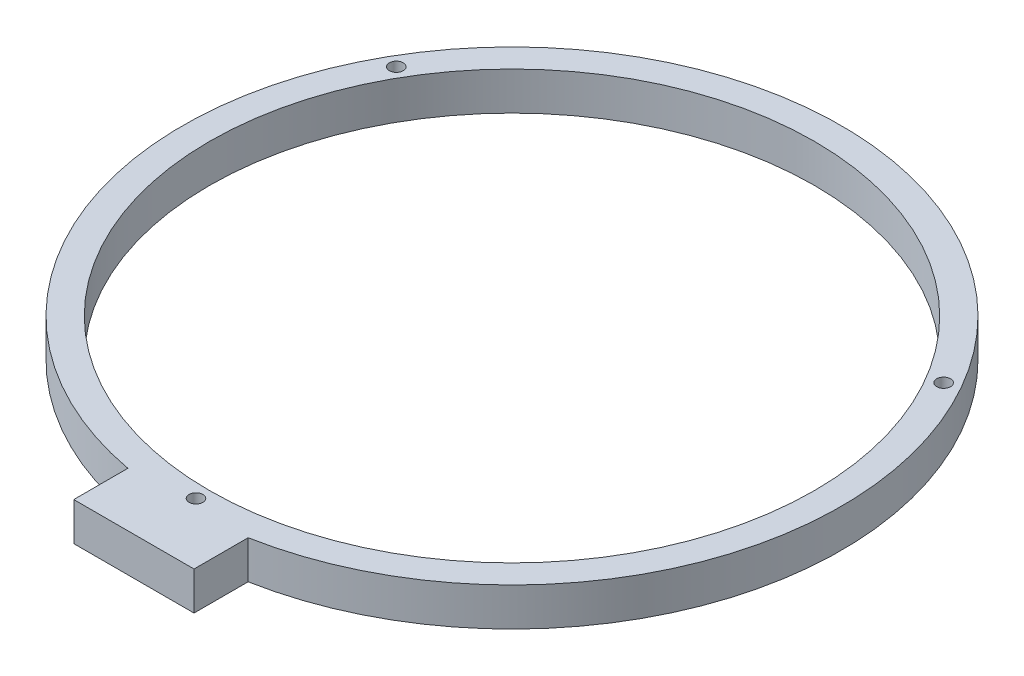
SolidWorks part; units mm, degrees
material "pla"
ref_plane "Front Plane" through (0, 0, 0) normal (0, 0, 1) x (1, 0, 0)
ref_plane "Top Plane" through (0, 0, 0) normal (0, 1, 0) x (1, 0, 0)
ref_plane "Right Plane" through (0, 0, 0) normal (1, 0, 0) x (0, 0, -1)
sketch "Sketch1" plane through (0, 0, 0) normal (0, 1, 0) x (1, 0, 0)
  line L0 (-10, -53.8799) -> (-10, -62.8799)
  line L1 (-10, -62.8799) -> (10, -62.8799)
  line L2 (10, -62.8799) -> (10, -53.8799)
  arc A0 (10, -53.8799) -> (-10, -53.8799) centre (0, 0) ccw
  circle A1 centre (0, 0) radius 50.3
  point P9 (0, -62.8799)
  dimension "D1" = 4.5
  dimension "D2" = 109.6
  dimension "D3" = 20
  dimension "D4" = 9
extrude "Boss-Extrude1" add sketch "Sketch1" along normal blind 6.35
sketch "Sketch2" plane through (0, 6.35, 0) normal (0, 1, 0) x (1, 0, 0)
  line L0 (0, -50.3) -> (0, -54.8) construction
  circle A0 centre (0, 0) radius 50.3 construction
  circle A1 centre (0, 0) radius 54.8 construction
  circle A2 centre (0, -52.55) radius 1.15
  dimension "D1" = 2.3
extrude "Cut-Extrude1" cut sketch "Sketch2" against normal up to next
pattern_circular "CirPattern1" count 3 over 360 about axis through (0, 6.35, 0) along (0, 1, 0) of "Cut-Extrude1"
sketch "Sketch3" plane through (0, 6.35, 0) normal (0, 1, 0) x (1, 0, 0)
  line L0 (-10, -53.8799) -> (-10, -49.2959)
  line L1 (41.3769, 35.9304) -> (37.9792, 32.9799)
  line L2 (0, 0) -> (41.3769, 35.9304) construction
  circle A0 centre (0, 0) radius 50.3 construction
  arc A1 (10, -53.8799) -> (-10, -53.8799) centre (0, 0) ccw construction
  circle A2 centre (0, 0) radius 54.8
  circle A3 centre (45.5096, 26.275) radius 1.15 construction
  circle A4 centre (0, 0) radius 50.3
  circle M5 centre (-45.5096, 26.275) radius 1.15
  arc M7 (10, -53.8799) -> (-10, -53.8799) centre (0, 0) ccw
  circle M11 centre (0, 0) radius 50.3
  dimension "D1" = 10
extrude "Cut-Extrude2" [suppressed] cut sketch "Sketch3" against normal up to next contours L1 L0 M7 M11 M5
